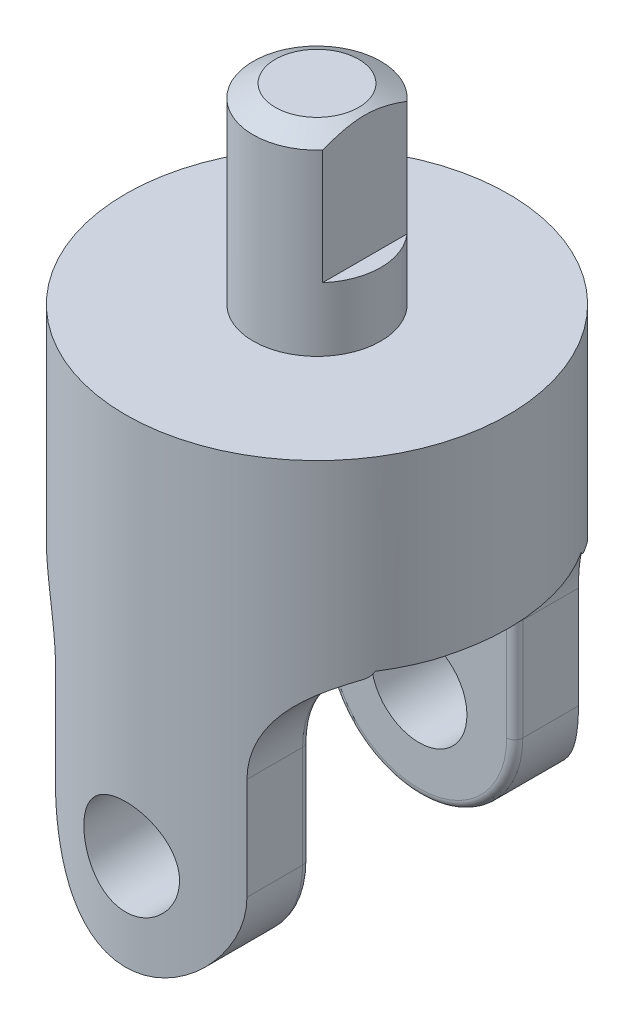
SolidWorks part; units mm, degrees
note: '?' marks a value the reader was unsure of.
ref_plane "Front" through (0, 0, 0) normal (0, 0, 1) x (1, 0, 0)
ref_plane "Top" through (0, 0, 0) normal (0, 1, 0) x (-1, 0, 0)
ref_plane "Right" through (0, 0, 0) normal (1, 0, 0) x (0, 0, -1)
sketch "Sketch1" plane through (0, 0, 0) normal (0, 1, 0) x (-1, 0, 0)
  circle A0 centre (0, 0) radius 19.05
  dimension "D1" = 38.1
extrude "Base-Extrude" add sketch "Sketch1" along normal blind 47.625
sketch "Sketch2" plane through (0, 0, 0) normal (0, 0, 1) x (1, 0, 0)
  line L0 (0, 0) -> (0, 23.7435) construction
  line L1 (9.525, 9.525) -> (9.525, 19.685)
  line L2 (-9.525, 9.525) -> (-9.525, 19.685)
  line L3 (19.05, 29.21) -> (19.05, -1.3662)
  line L4 (19.05, -1.3662) -> (-19.05, -1.3662)
  line L5 (-19.05, -1.3662) -> (-19.05, 29.21)
  line L6 (19.05, 0) -> (-19.05, 0) construction
  arc A0 (-9.525, 9.525) -> (9.525, 9.525) centre (0, 9.525) ccw
  arc A1 (9.525, 19.685) -> (19.05, 29.21) centre (19.05, 19.685) cw
  arc A2 (-9.525, 19.685) -> (-19.05, 29.21) centre (-19.05, 19.685) ccw
  dimension "D3" = 9.525
  dimension "D1" = 38.1
  dimension "D2" = 19.05
  dimension "D4" = 29.21
extrude "Cut-Extrude1" cut sketch "Sketch2" against normal through all and the other way through all
sketch "Sketch8" plane through (0, 0, 0) normal (1, 0, 0) x (0, 0, -1)
  line L0 (-10.16, -7.4553) -> (10.16, -7.4553)
  line L1 (-10.16, -7.4553) -> (-10.16, 29.1452)
  line L2 (10.16, 29.1452) -> (-10.16, 29.1452)
  line L3 (10.16, 29.1452) -> (10.16, -7.4553)
  point P4 (0, 0)
  dimension "D1" = 10.16
  dimension "D2" = 20.32
extrude "Cut-Extrude5" cut sketch "Sketch8" against normal through all and the other way blind 47.625
fillet "Fillet1" radius 0.8001 16 edges at (0, 0, -10.16) (0, 0, 10.16) (12.2929, 26.3982, 14.5529) (-12.2929, 26.3982, 14.5529) (9.525, 14.605, 10.16) (11.3465, 25.287, 10.16) (11.3465, 25.287, -10.16) (9.525, 14.605, -10.16) (16.1145, 28.9458, 10.16) (-9.525, 14.605, 10.16) (-11.3465, 25.287, 10.16) (-16.1145, 28.9458, 10.16) (16.1145, 28.9458, -10.16) (-16.1145, 28.9458, -10.16) (-11.3465, 25.287, -10.16) (-9.525, 14.605, -10.16)
sketch "Sketch11" plane through (0, 0, 0) normal (0, 0, 1) x (1, 0, 0)
  circle A0 centre (0, 9.525) radius 4.7625
  dimension "D1" = 9.525
extrude "Cut-Extrude6" cut sketch "Sketch11" against normal through all and the other way through all
sketch "Sketch12" plane through (0, 47.625, 0) normal (0, 1, 0) x (-1, 0, 0)
  circle A0 centre (0, 0) radius 6.35
  dimension "D1" = 12.7
extrude "Boss-Extrude1" add sketch "Sketch12" along normal blind 19.05
chamfer "Chamfer3" distance 1.27 angle 60 1 edges at (0, 66.675, 6.35) first distance on face at (0, 66.675, 6.35)
ref_axis "Axis1" through (0, 97.625, 0) along (0, -1, 0)?
sketch "Sketch13" plane through (0, 66.675, 0) normal (0, 1, 0) x (-1, 0, 0)
  line L0 (-4.7625, 4.2001) -> (-4.7625, -4.2001)
  circle A0 centre (0, 0) radius 6.35 construction
  arc A1 (-4.7625, 4.2001) -> (-4.7625, -4.2001) centre (0, 0) ccw
  dimension "D1" = 1.5875
extrude "Cut-Extrude7" cut sketch "Sketch13" against normal blind 12.7
